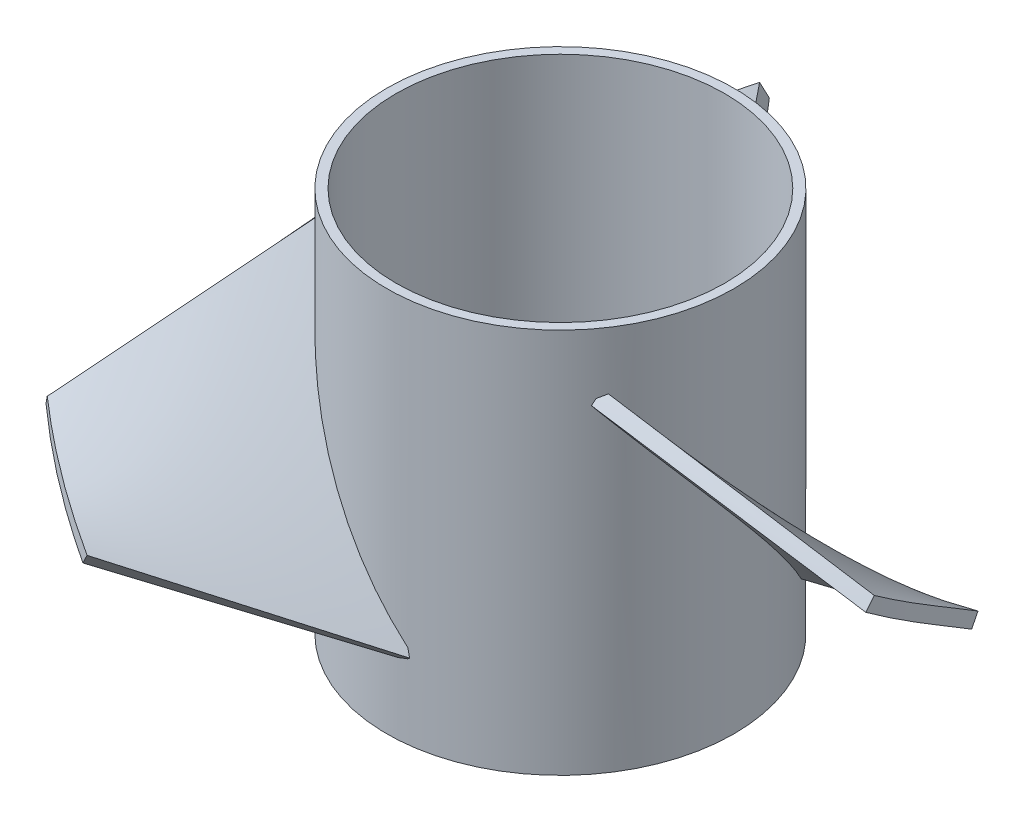
SolidWorks part; units mm, degrees
material "ABS"
ref_plane "Front Plane" through (0, 0, 0) normal (0, 0, 1) x (1, 0, 0)
ref_plane "Top Plane" through (0, 0, 0) normal (0, 1, 0) x (1, 0, 0)
ref_plane "Right Plane" through (0, 0, 0) normal (1, 0, 0) x (0, 0, -1)
ref_plane "Plane1" through (12, 0, 0) normal (1, 0, 0) x (0, 0, -1)
sketch "Sketch3" plane through (12, 0, 0) normal (1, 0, 0) x (0, 0, -1)
  line L0 (-8.8586, 10.8409) -> (8.8586, -10.8409) construction
  line L1 (-9.3232, 10.4612) -> (-8.394, 11.2205)
  line L2 (0, 0) -> (3.248, 2.6541) construction
  line L3 (-8.394, 11.2205) -> (9.3232, -10.4612)
  line L4 (-9.3232, 10.4612) -> (8.394, -11.2205)
  line L5 (8.394, -11.2205) -> (9.3232, -10.4612)
  point P4 (0, 0)
  point P6 (-8.8586, 10.8409)
  point P12 (-0.4646, -0.3797)
  point P13 (0.4646, 0.3797)
  dimension "D1" = 1.2
ref_plane "Plane2" through (32, 0, 0) normal (1, 0, 0) x (0, 0, -1)
sketch "Sketch4" plane through (32, 0, 0) normal (1, 0, 0) x (0, 0, -1)
  line L0 (-4.3217, 2.5145) -> (4.3217, -2.5145) construction
  line L2 (-4.6234, 1.9959) -> (-4.0199, 3.0332)
  line L3 (0, 0) -> (0.826, 1.4196) construction
  line L4 (-4.0199, 3.0332) -> (4.6234, -1.9959)
  line L5 (-4.6234, 1.9959) -> (4.0199, -3.0332)
  line L6 (4.0199, -3.0332) -> (4.6234, -1.9959)
  point P4 (0, 0)
  point P8 (-4.3217, 2.5145)
  point P13 (-0.3017, -0.5186)
  point P14 (0.3017, 0.5186)
  dimension "D1" = 1.2
loft "Loft2" add profiles "Sketch3", "Sketch4" connector at (12, 11.2205, 8.394) connector at (32, 3.0332, 4.0199)
sketch "Sketch6" plane through (0, 0, 0) normal (0, 1, 0) x (1, 0, 0)
  circle A0 centre (0, 0) radius 14.5
extrude "Cut-Extrude1" cut sketch "Sketch6" against normal blind 20 and the other way blind 20.0001
sketch "Sketch5" plane through (0, 0, 0) normal (0, 1, 0) x (1, 0, 0)
  circle A0 centre (0, 0) radius 14.15
extrude "Extrude-Thin3" add sketch "Sketch5" along normal blind 16 and the other way blind 12 thin contours A0 thin type one direction wall 0.8
pattern_circular "CirPattern5" count 3 over 360 about axis through (0, 16, 0) along (0, 1, 0) of "Loft2", "Cut-Extrude1"
sketch "Sketch7" plane through (0, 0, 0) normal (0, 1, 0) x (1, 0, 0)
  circle A2 centre (0, 0) radius 14.15
extrude "Extrude-Thin4" add sketch "Sketch7" along normal blind 16 and the other way blind 16 thin thin type one direction wall 0.8
sketch "Sketch8" plane through (0, -16, 0) normal (0, -1, 0) x (1, 0, 0)
  circle A2 centre (0, 0) radius 14.95 construction
  circle A3 centre (0, 0) radius 14.95
extrude "Boss-Extrude1" add sketch "Sketch8" along normal blind 1.2
sketch "Sketch9" plane through (0, -17.2, 0) normal (0, -1, 0) x (1, 0, 0)
  line L0 (0, 0) -> (4.9441, 7.5204) construction
  line L1 (0, 0) -> (-6.6625, 4.3802)
  circle A0 centre (4.9441, 7.5204) radius 1.5
  circle A1 centre (-4.9441, -7.5204) radius 1.5
extrude "Cut-Extrude2" cut sketch "Sketch9" against normal blind 1.2 and the other way blind 1.2 contours A1 | A0 region at (4.9441, -17.2, 7.5204) region at (-4.9441, -17.2, -7.5204)
sketch "Sketch10" plane through (0, -17.2, 0) normal (0, -1, 0) x (1, 0, 0)
  circle A0 centre (0, 0) radius 5
extrude "Cut-Extrude3" cut sketch "Sketch10" against normal blind 11.2 and the other way blind 1.2
sketch "Sketch11" plane through (0, -17.2, 0) normal (0, 1, 0) x (1, 0, 0)
  circle A0 centre (0, 0) radius 31.5
extrude "Cut-Extrude-Thin1" cut sketch "Sketch11" against normal blind 10 and the other way blind 38 thin thin type one direction wall 10
